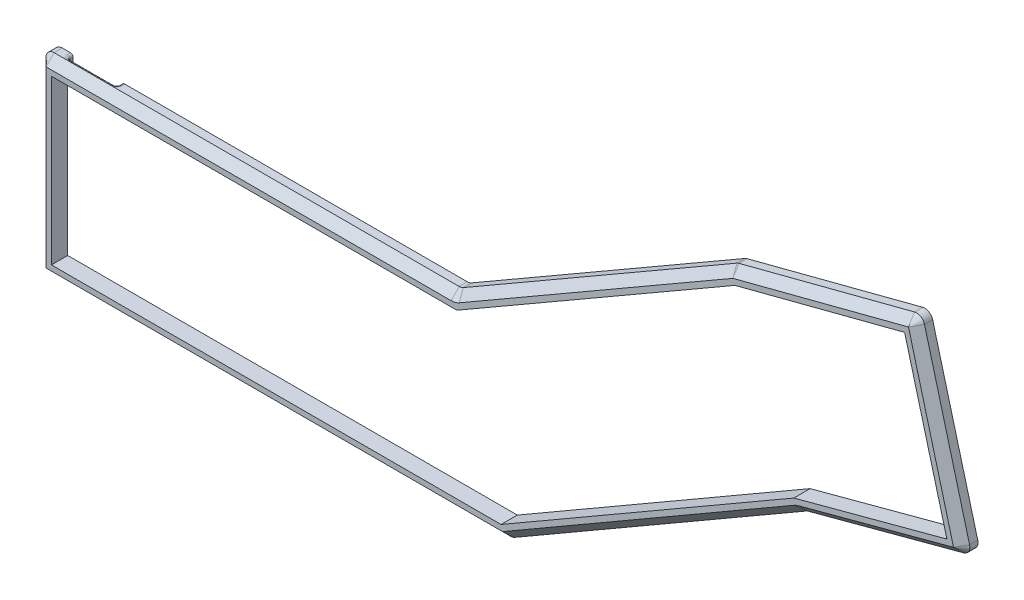
SolidWorks part; units mm, degrees
ref_plane "Plan de face" through (0, 0, 0) normal (0, 0, 1) x (1, 0, 0)
ref_plane "Plan de dessus" through (0, 0, 0) normal (0, 1, 0) x (1, 0, 0)
ref_plane "Plan de droite" through (0, 0, 0) normal (1, 0, 0) x (0, 0, -1)
sketch "Esquisse1" plane through (0, 0, 0) normal (0, 0, 1) x (1, 0, 0)
  line L0 (152.8114, 25.9717) -> (138.2826, 80.2215) construction
  line L1 (98.1506, 11.3316) -> (152.8114, 25.9717) construction
  line L2 (-9.3986, -50.8585) -> (98.1506, 11.3316) construction
  line L3 (-172.3739, -50.8585) -> (-9.3986, -50.8585) construction
  line L4 (-24.5886, 5.3017) -> (-172.3739, 5.2915) construction
  line L5 (138.2826, 80.2215) -> (78.0109, 64.5416) construction
  line L6 (-151.6088, 5.3124) -> (-151.6088, 5.2929)
  line L7 (-24.5886, 5.3017) -> (78.0109, 64.5416) construction
  line L8 (-172.3739, 5.2915) -> (-172.3739, -50.6876) construction
  line L9 (-172.3739, -50.6876) -> (-172.3739, -50.8585) construction
  line L10 (-25.1245, 7.3016) -> (-174.3739, 7.2914)
  line L11 (-174.3739, 7.2914) -> (-174.3739, -50.6876)
  line L12 (-174.3739, -50.6876) -> (-174.3739, -52.8585)
  line L13 (-174.3739, -52.8585) -> (-8.862, -52.8585)
  line L14 (-8.862, -52.8585) -> (98.9231, 9.4681)
  line L15 (98.9231, 9.4681) -> (155.2607, 24.5572)
  line L16 (155.2607, 24.5572) -> (139.7008, 82.657)
  line L17 (139.7008, 82.657) -> (77.2454, 66.409)
  line L18 (-25.1245, 7.3016) -> (77.2454, 66.409)
  line L19 (-26.4645, 12.3015) -> (-179.3739, 12.291)
  line L20 (-179.3739, 12.291) -> (-179.3739, -50.6876)
  line L21 (-179.3739, -50.6876) -> (-179.3739, -57.8585)
  line L22 (-179.3739, -57.8585) -> (-7.5204, -57.8585)
  line L23 (-7.5204, -57.8585) -> (100.8545, 4.8091)
  line L24 (100.8545, 4.8091) -> (161.3839, 21.021)
  line L25 (161.3839, 21.021) -> (143.2464, 88.7459)
  line L26 (143.2464, 88.7459) -> (75.3314, 71.0775)
  line L27 (-26.4645, 12.3015) -> (75.3314, 71.0775)
  circle A0 centre (80.6856, 58.4893) radius 1
  circle A1 centre (92.8776, 28.0855) radius 1
  circle A2 centre (-29.7028, -2.6485) radius 1
  circle A3 centre (-10.6528, -46.4381) radius 1
  circle A4 centre (-114.2594, -13.4181) radius 1
  circle A5 centre (-114.0308, -32.4935) radius 1
  dimension "D1" = 2
  dimension "D2" = 5
extrude "Boss.-Extru.1" add sketch "Esquisse1" along normal blind 6 contours L27 L19 L20 L21 L22 L23 L24 L25 L26 L10 L18 L17 L16 L15 L14 L13 L12 L11 region at (26.2883, 38.477, 0)
fillet "Congé1" radius 3 8 edges at (-179.3739, -57.8585, 3) (-7.5204, -57.8585, 3) (100.8545, 4.8091, 3) (161.3839, 21.021, 3) (143.2464, 88.7459, 3) (75.3314, 71.0775, 3) (-26.4645, 12.3015, 3) (-179.3739, 12.291, 3)
sketch "Esquisse2" plane through (0, 0, 0) normal (0, 0, 1) x (1, 0, 0)
  circle A0 centre (158.2016, 22.9581) radius 1
  circle A1 centre (141.3885, 85.5343) radius 1
  circle A2 centre (76.5002, 68.7766) radius 1
  circle A3 centre (99.8904, 7.0714) radius 1
  circle A4 centre (-8.1724, -55.2759) radius 1
  circle A5 centre (-25.6914, 9.9201) radius 1
  circle A6 centre (-176.5621, 9.9201) radius 1
  circle A7 centre (-177.0296, -55.2759) radius 1
extrude "Enlèv. mat.-Extru.1" cut sketch "Esquisse2" along normal blind 3
chamfer "Chanfrein1" distance 3 angle 45 16 edges at (-178.4953, 11.4125, 6) (-101.8212, 12.2964, 6) (-26.4919, 12.4038, 6) (24.6056, 41.7889, 6) (75.3418, 71.0522, 6) (108.0441, 79.5878, 6) (142.6286, 87.6851, 6) (152.3124, 54.8937, 6) (160.3079, 21.6424, 6) (129.8616, 12.5782, 6) (100.8645, 4.785, 6) (46.844, -26.4224, 6) (-7.5479, -57.756, 6) (-92.3496, -57.8585, 6) (-178.4952, -56.9798, 6) (-179.3739, -22.7836, 6)
sketch "Esquisse3" plane through (-0.0008, 12.3034, 0) normal (-0.0001, 1, 0) x (1, 0.0001, 0)
  line L0 (-176.3732, 0) -> (-176.3732, -3) construction
  line L1 (-172.3732, 0) -> (-154.3732, 0)
  line L2 (-172.3732, 0) -> (-172.3732, -1)
  line L3 (-171.3732, -2) -> (-155.3732, -2)
  line L4 (-154.3732, 0) -> (-154.3732, -1)
  line L5 (-27.2675, 0) -> (-176.3732, 0) construction
  arc A0 (-155.3732, -2) -> (-154.3732, -1) centre (-155.3732, -1) ccw
  arc A1 (-172.3732, -1) -> (-171.3732, -2) centre (-171.3732, -1) ccw
  point P10 (-154.3732, -2)
  dimension "D5" = 1
  dimension "D1" = 4
  dimension "D2" = 18
  dimension "D3" = 0
  dimension "D4" = 2
extrude "Enlèv. mat.-Extru.2" cut sketch "Esquisse3" against normal blind 10
fillet "Congé3" radius 1 5 edges at (-154.3741, 12.2928, 0.5) (-154.667, 12.2927, 1.7071) (-163.3741, 12.2921, 2) (-172.0812, 12.2915, 1.7071) (-172.3741, 12.2915, 0.5)
